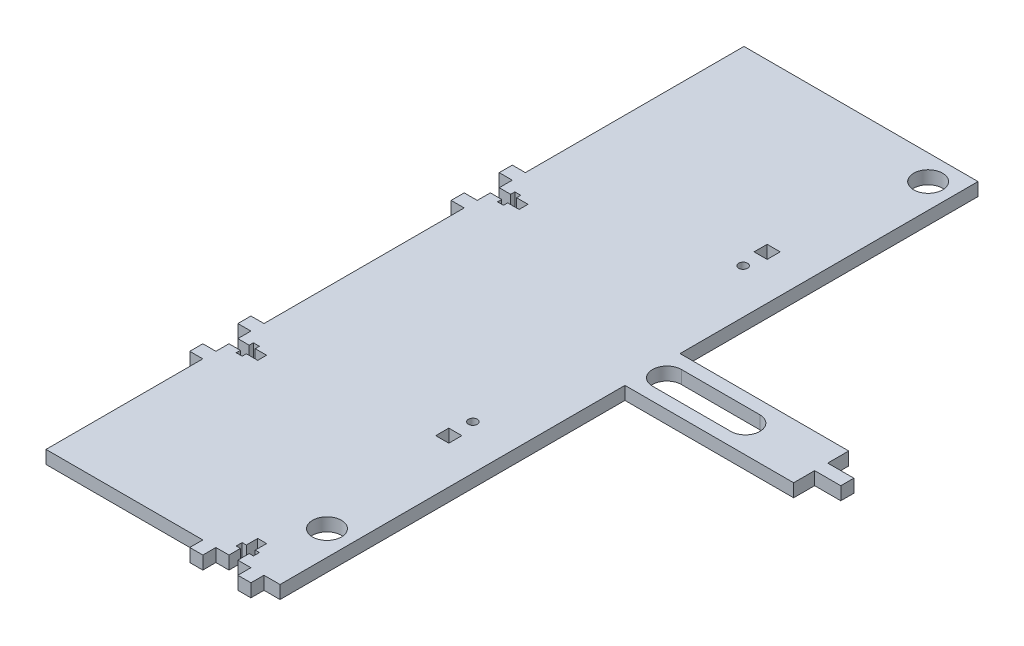
SolidWorks part; units mm, degrees
ref_plane "Front Plane" through (0, 0, 0) normal (0, 0, 1) x (1, 0, 0)
ref_plane "Top Plane" through (0, 0, 0) normal (0, 1, 0) x (1, 0, 0)
ref_plane "Right Plane" through (0, 0, 0) normal (1, 0, 0) x (0, 0, -1)
sketch "Axle Support Plate" plane through (0, 0, 0) normal (0, 1, 0) x (1, 0, 0)
  line L0 (25.4, 146.05) -> (25.4, -146.05) construction
  line L1 (12.7, 158.1601) -> (12.7, -187.325) construction
  line L2 (12.7, -80.518) -> (12.7, -74.168)
  line L3 (12.7, 80.518) -> (19.05, 80.518)
  line L4 (37.5101, -180.975) -> (37.5101, -13.3801)
  line L5 (0, 0) -> (37.5101, 158.1601) construction
  line L6 (0, 0) -> (37.5101, -180.975) construction
  line L7 (-76.2, -75.057) -> (-76.2, 22.225)
  line L8 (-76.2, 158.1601) -> (37.5101, 158.1601)
  line L9 (6.35, -180.975) -> (12.7, -180.975)
  line L10 (12.7, 80.518) -> (12.7, 74.168)
  line L11 (12.7, 74.168) -> (19.05, 74.168)
  line L12 (0, -187.325) -> (0, -180.975)
  line L13 (19.05, 80.518) -> (19.05, 74.168)
  line L14 (12.7, -80.518) -> (19.05, -80.518)
  line L15 (19.05, -80.518) -> (19.05, -74.168)
  line L16 (12.7, -74.168) -> (19.05, -74.168)
  line L17 (37.5101, 0) -> (0, 0) construction
  line L18 (0, -187.325) -> (6.35, -187.325)
  line L19 (6.35, -187.325) -> (6.35, -180.975)
  line L20 (23.368, -180.975) -> (23.368, -187.325)
  line L21 (23.368, -187.325) -> (29.718, -187.325)
  line L22 (29.718, -187.325) -> (29.718, -180.975)
  line L23 (29.718, -180.975) -> (37.5101, -180.975)
  line L24 (15.875, 80.518) -> (15.875, 65.659) construction
  line L25 (12.7, -180.975) -> (12.7, -175.44)
  line L26 (12.7, -175.44) -> (10.659, -175.44)
  line L27 (10.659, -175.44) -> (10.659, -172.54)
  line L28 (10.659, -172.54) -> (12.7, -172.54)
  line L29 (12.7, -172.54) -> (12.7, -167.005)
  line L30 (12.7, -167.005) -> (17.018, -167.005)
  line L31 (17.018, -167.005) -> (17.018, -172.54)
  line L32 (17.018, -172.54) -> (19.059, -172.54)
  line L33 (19.059, -172.54) -> (19.059, -175.44)
  line L34 (19.059, -175.44) -> (17.018, -175.44)
  line L35 (17.018, -175.44) -> (17.018, -180.975)
  line L36 (17.018, -180.975) -> (23.368, -180.975)
  line L37 (37.5101, 13.3801) -> (119.4703, 13.3801)
  line L38 (119.4703, 13.3801) -> (119.4703, 3.175)
  line L39 (119.4703, -13.3801) -> (37.5101, -13.3801)
  line L40 (44.5403, 0) -> (82.6403, 0) construction
  line L41 (44.5403, 7.0301) -> (82.6403, 7.0301)
  line L42 (44.5403, -7.0301) -> (82.6403, -7.0301)
  line L43 (119.4703, -3.175) -> (132.1703, -3.175)
  line L44 (132.1703, -3.175) -> (132.1703, 3.175)
  line L45 (132.1703, 3.175) -> (119.4703, 3.175)
  line L46 (37.5101, 13.3801) -> (37.5101, 158.1601)
  line L47 (37.5101, 13.3801) -> (37.5101, -13.3801) construction
  line L48 (37.5101, 0) -> (132.1703, 0) construction
  line L51 (119.4703, -3.175) -> (119.4703, -13.3801)
  line L81 (-76.2, 51.943) -> (-76.2, 158.1601)
  line L90 (0, -180.975) -> (-76.2, -180.975)
  line L94 (-76.2, -180.975) -> (-76.2, -104.775)
  circle A0 centre (25.4, 146.05) radius 7.0301
  circle A1 centre (25.4, -146.05) radius 7.0301
  circle A2 centre (15.875, 65.659) radius 2.159
  circle A3 centre (15.875, -65.659) radius 2.159
  arc A4 (44.5403, 7.0301) -> (44.5403, -7.0301) centre (44.5403, 0) ccw
  arc A5 (82.6403, -7.0301) -> (82.6403, 7.0301) centre (82.6403, 0) ccw
  point P0 (0, 0)
  point P15 (25.4, 0)
  point P38 (15.875, 67.818)
  point P57 (63.5903, 0)
  line B0 (-76.2, -81.407) -> (-82.55, -81.407)
  line B1 (-82.55, -81.407) -> (-82.55, -75.057)
  line B2 (-82.55, -75.057) -> (-76.2, -75.057)
  line B3 (-76.2, -87.757) -> (-70.665, -87.757)
  line B4 (-70.665, -87.757) -> (-70.665, -85.716)
  line B5 (-70.665, -85.716) -> (-67.765, -85.716)
  line B6 (-67.765, -85.716) -> (-67.765, -87.757)
  line B7 (-67.765, -87.757) -> (-62.23, -87.757)
  line B8 (-62.23, -87.757) -> (-62.23, -92.075)
  line B9 (-62.23, -92.075) -> (-67.765, -92.075)
  line B10 (-67.765, -92.075) -> (-67.765, -94.116)
  line B11 (-67.765, -94.116) -> (-70.665, -94.116)
  line B12 (-70.665, -94.116) -> (-70.665, -92.075)
  line B13 (-70.665, -92.075) -> (-76.2, -92.075)
  line B14 (-62.23, -89.916) -> (-76.2, -89.916) construction
  line B15 (-76.2, -98.425) -> (-76.2, -92.075)
  line B16 (-82.55, -104.775) -> (-76.2, -104.775)
  line B17 (-76.2, -81.407) -> (-76.2, -87.757)
  line B18 (-82.55, -98.425) -> (-82.55, -104.775)
  line B19 (-76.2, -98.425) -> (-82.55, -98.425)
  line B20 (-76.2, 45.593) -> (-82.55, 45.593)
  line B21 (-82.55, 45.593) -> (-82.55, 51.943)
  line B22 (-82.55, 51.943) -> (-76.2, 51.943)
  line B23 (-76.2, 39.243) -> (-70.665, 39.243)
  line B24 (-70.665, 39.243) -> (-70.665, 41.284)
  line B25 (-70.665, 41.284) -> (-67.765, 41.284)
  line B26 (-67.765, 41.284) -> (-67.765, 39.243)
  line B27 (-67.765, 39.243) -> (-62.23, 39.243)
  line B28 (-62.23, 39.243) -> (-62.23, 34.925)
  line B29 (-62.23, 34.925) -> (-67.765, 34.925)
  line B30 (-67.765, 34.925) -> (-67.765, 32.884)
  line B31 (-67.765, 32.884) -> (-70.665, 32.884)
  line B32 (-70.665, 32.884) -> (-70.665, 34.925)
  line B33 (-70.665, 34.925) -> (-76.2, 34.925)
  line B34 (-62.23, 37.084) -> (-76.2, 37.084) construction
  line B35 (-76.2, 28.575) -> (-76.2, 34.925)
  line B36 (-82.55, 22.225) -> (-76.2, 22.225)
  line B37 (-76.2, 45.593) -> (-76.2, 39.243)
  line B38 (-82.55, 28.575) -> (-82.55, 22.225)
  line B39 (-76.2, 28.575) -> (-82.55, 28.575)
  dimension "D1" = 5.08
  dimension "D4" = 14.0603
  dimension "D5" = 5.08
  dimension "D8" = 63.5
  dimension "D14" = 14.0603
  dimension "D15" = 4.318
  dimension "D16" = 6.35
  dimension "D22" = 7.0301
  dimension "D25" = 36.83
  dimension "D2" = 292.1
  dimension "D3" = 6.35
  dimension "D6" = 12.7
  dimension "D7" = 6.35
  dimension "D9" = 12.7
  dimension "D10" = 6.35
  dimension "D11" = 6.35
  dimension "D12" = 13.97
  dimension "D13" = 34.925
  dimension "D17" = 4.318
  dimension "D18" = 8.4
  dimension "D19" = 2.9
  dimension "D20" = 6.35
  dimension "D21" = 6.35
  dimension "D23" = 6.35
  dimension "D24" = 38.1
  dimension "D26" = 12.7
  dimension "D27" = 6.35
  dimension "D28" = 101.6
  dimension "D29" = 76.2
  dimension "D30" = 203.2
sketch_block_instance "Male T-slot assembly-1"
sketch_block "Male T-slot assembly" parameters "D1"=6.35, "D2"=6.35, "D3"=4.318, "D4"=2.9, "D5"=8.4, "D6"=13.97, "D7"=6.35
sketch_block_instance "Male T-slot assembly-2"
extrude "Boss-Extrude1" add sketch "Axle Support Plate" along normal blind 6.35 contours L12 L18 L19 L9 L25 L26 L27 L28 L29 L30 L31 L32 L33 L34 L35 L36 L20 L21 L22 L23 L4 L39 L51 L43 L44 L45 L38 L37 L46 L8 region at (-15.5961, 0, 11.1356)
equation "\"Ball Diameter\"= 1.75in"
equation "\"Sheet Thickness\"= 0.25in"
equation "\"Screw Diameter\"= .17in"
equation "\"Robot Diameter\"= 14in"
equation "\"Castor Screw Diameter\"= 0.22in"
equation "\"Wheel Diameter\" = 4in"
equation "\"Nut Diameter\" = 8.4mm"
equation "\"Nut Height\" = 2.9mm"
equation "\"Screw Height\" = 0.55in"
equation "\"Pulley Diameter\" = 1in"
equation "\"Reactor Height\" = 14in"
equation "\"Elevator Height\" = 11.5in"
equation "\"Elevator Width\" = \"Ball Diameter\" + 0.25in"
equation "\"D1@Boss-Extrude1\"=\"Sheet Thickness\""
equation "\"Elevator Bearing Diameter\" = sqr(2*(\"Sheet Thickness\"^2)) + 0.2in"
equation "\"Elevator Axle Length\" = \"Elevator Width\" + 8*\"Sheet Thickness\""
equation "\"D4@Axle Support Plate\"=\"Elevator Bearing Diameter\""
equation "\"D6@Axle Support Plate\"=(\"Pulley Diameter\")/2"
equation "\"D3@Axle Support Plate\"=\"Sheet Thickness\""
equation "\"D7@Axle Support Plate\"=\"Sheet Thickness\""
equation "\"D10@Axle Support Plate\"=\"Sheet Thickness\""
equation "\"D11@Axle Support Plate\"=\"Sheet Thickness\""
equation "\"D12@Axle Support Plate\"=\"Screw Height\""
equation "\"D13@Axle Support Plate\"=2.5in - \"Sheet Thickness\" - (\"Ball Diameter\")/2"
equation "\"D9@Axle Support Plate\"=2*\"Sheet Thickness\""
equation "\"D14@Axle Support Plate\"=\"Elevator Bearing Diameter\""
equation "\"D15@Axle Support Plate\"=\"Screw Diameter\""
equation "\"D16@Axle Support Plate\"=\"Sheet Thickness\""
equation "\"D17@Axle Support Plate\"=\"Screw Diameter\""
equation "\"D18@Axle Support Plate\"=\"Nut Diameter\""
equation "\"D19@Axle Support Plate\"=\"Nut Height\""
equation "\"D20@Axle Support Plate\"=\"Sheet Thickness\""
equation "\"D21@Axle Support Plate\"=\"Sheet Thickness\""
equation "\"D22@Axle Support Plate\"=\"Elevator Bearing Diameter\"/2"
equation "\"D23@Axle Support Plate\"=\"Sheet Thickness\""
equation "\"Elevator Axle Endcap Diameter\" = \"Pulley Diameter\" + 0.25in"
equation "\"D25@Axle Support Plate\"=\"Elevator Axle Endcap Diameter\"+0.2in"
equation "\"D27@Axle Support Plate\"=\"Sheet Thickness\""
equation "\"Elevator Clearance from Axis\" = (\"Pulley Diameter\"/2) + \"Ball Diameter\" + 0.5in"
equation "\"D28@Axle Support Plate\"=\"Elevator Clearance from Axis\" + \"Sheet Thickness\" + 1in"
